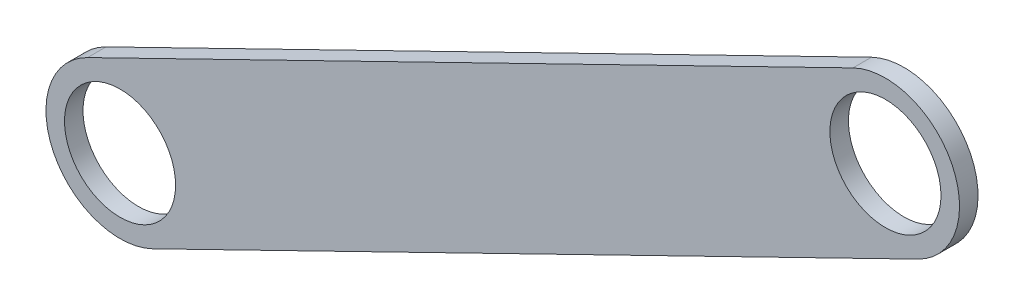
SolidWorks part; units mm, degrees
ref_plane "Front Plane" through (0, 0, 0) normal (0, 0, 1) x (1, 0, 0)
ref_plane "Top Plane" through (0, 0, 0) normal (0, 1, 0) x (1, 0, 0)
ref_plane "Right Plane" through (0, 0, 0) normal (1, 0, 0) x (0, 0, -1)
sketch "Esquisse2" plane through (0, 0, 0) normal (0, 0, 1) x (1, 0, 0)
  line L0 (0, -12) -> (-41.3354, -32.1839) construction
  line L1 (1.7551, -15.5944) -> (-39.5802, -35.7782)
  line L2 (-1.7551, -8.4056) -> (-43.0905, -28.5895)
  arc A0 (1.7551, -15.5944) -> (-1.7551, -8.4056) centre (0, -12) ccw
  arc A1 (-43.0905, -28.5895) -> (-39.5802, -35.7782) centre (-41.3354, -32.1839) ccw
  circle A2 centre (0, -12) radius 3
  circle A3 centre (-41.3354, -32.1839) radius 3
  point P4 (-20.6677, -22.0919)
  dimension "D2" = 6
  dimension "D3" = 6
  dimension "D1" = 8
base flange "Tôle de base pliée1" sketch "Esquisse2" thickness 1 reverse thickness direction yes parameters "D1"=0.7366
sketch "Bend-Lines1" [suppressed] plane through (0, 0, 0) normal (0, 1, 0) x (1, 0, 0)
sketch "Bounding-Box1" [suppressed] plane through (0, 0, 0) normal (0, 1, 0) x (1, 0, 0)
sheet metal parameters "Sheet-Metal1" thickness 1 parameters "D1"=0.7366
flat pattern "Flat-Pattern1" [suppressed]
sketch "Bend-Lines2" plane through (0, 0, 0) normal (0, 1, 0) x (1, 0, 0)
sketch3d "Bounding-Box2" [suppressed]
  line L0 (43.1746, -25.5333, 0) -> (-5.3495, -1.8393, 0) construction
  line L1 (46.6848, -18.3446, 0) -> (-1.8392, 5.3495, 0) construction
  line L2 (43.1746, -25.5333, 0) -> (46.6848, -18.3446, 0) construction
  line L3 (-5.3495, -1.8393, 0) -> (-1.8392, 5.3495, 0) construction
